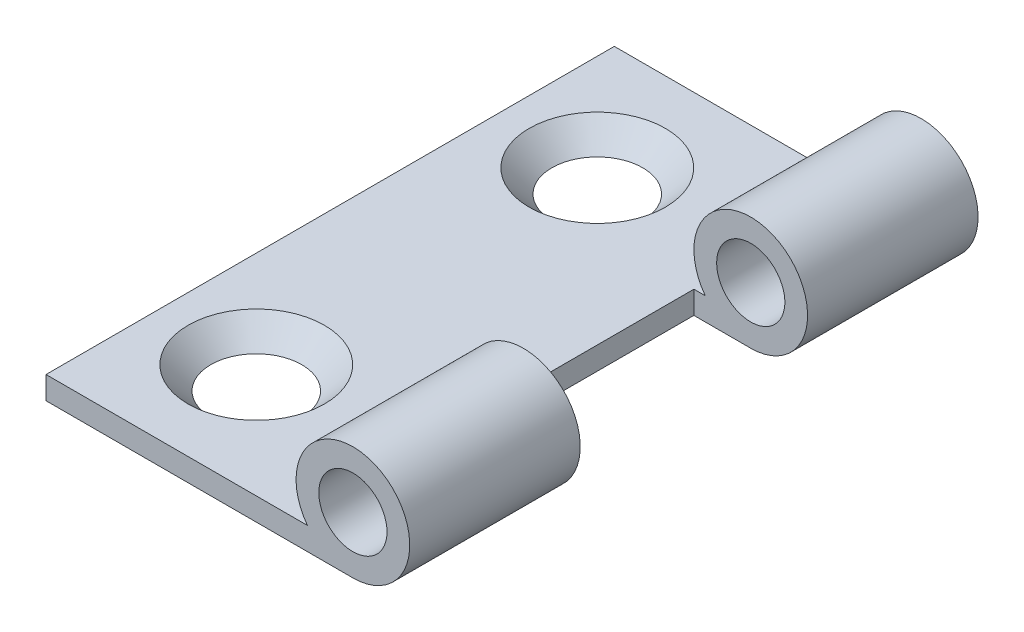
SolidWorks part; units mm, degrees
ref_plane "前视基准面" through (0, 0, 0) normal (0, 0, 1) x (1, 0, 0)
ref_plane "上视基准面" through (0, 0, 0) normal (0, 1, 0) x (1, 0, 0)
ref_plane "右视基准面" through (0, 0, 0) normal (1, 0, 0) x (0, 0, -1)
sketch "草图1" plane through (0, 0, 0) normal (0, 0, 1) x (1, 0, 0)
  line L0 (0, -2.5) -> (-13.5, -2.5)
  line L1 (-13.5, -2.5) -> (-13.5, -1.5)
  line L2 (-13.5, -1.5) -> (-2, -1.5)
  arc A0 (0, -2.5) -> (-2, -1.5) centre (0, 0) ccw
  circle A1 centre (0, 0) radius 1.5
  dimension "D3" = 5
  dimension "D4" = 3
  dimension "D1" = 1
  dimension "D2" = 13.5
extrude "凸台-拉伸1" add sketch "草图1" along normal blind 25
sketch "草图2" plane through (0, -1.5, 0) normal (0, 1, 0) x (1, 0, 0)
  line L0 (-13.5, -12.5) -> (2.5, -12.5) construction
  line L1 (-13.5, -25) -> (-13.5, 0) construction
  line L2 (2.5, -25) -> (2.5, 0) construction
  line L4 (-2.5, -17.5) -> (2.5, -17.5)
  line L5 (-2.5, -17.5) -> (-2.5, -7.5)
  line L6 (-2.5, -7.5) -> (2.5, -7.5)
  line L7 (2.5, -17.5) -> (2.5, -7.5)
  line L8 (-2.5, -17.5) -> (2.5, -7.5) construction
  line L9 (-2.5, -7.5) -> (2.5, -17.5) construction
  circle A0 centre (-9.25, -5) radius 2
  circle A1 centre (-9.25, -20) radius 2
  point P11 (0, -12.5)
  dimension "D2" = 4
  dimension "D1" = 15
  dimension "D3" = 9.25
  dimension "D4" = 10
  dimension "D5" = 5
extrude "切除-拉伸1" cut sketch "草图2" against normal mid plane 15
chamfer "倒角1" distance 1 angle 45 2 edges at (-7.25, -1.5, 20) (-7.25, -1.5, 5)
